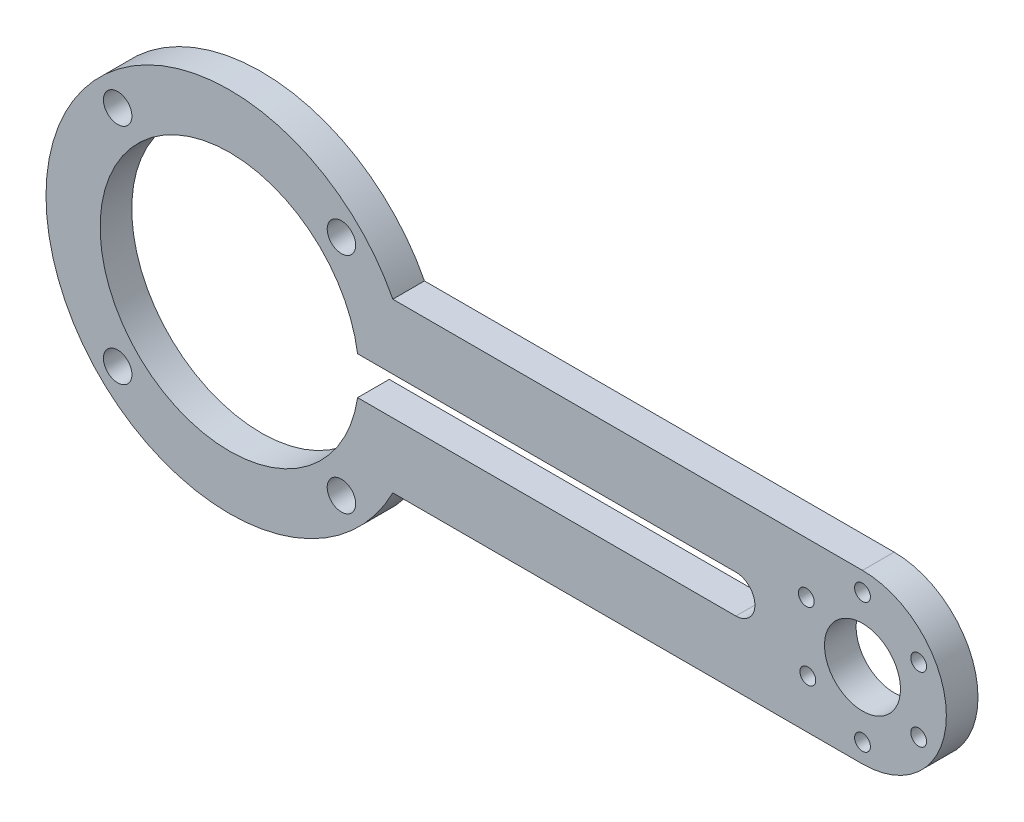
SolidWorks part; units mm, degrees
material "Wrought Stainless Steel"
ref_plane "Front Plane" through (0, 0, 0) normal (0, 0, 1) x (1, 0, 0)
ref_plane "Top Plane" through (0, 0, 0) normal (0, 1, 0) x (1, 0, 0)
ref_plane "Right Plane" through (0, 0, 0) normal (1, 0, 0) x (0, 0, -1)
sketch "Sketch2" plane through (0, 0, 0) normal (0, 0, 1) x (1, 0, 0)
  line L0 (0, 13.25) -> (100, 13.25)
  line L1 (0, -13.25) -> (100, -13.25)
  line L2 (50, 0) -> (50, -3)
  line L3 (50, 0) -> (50, 3)
  line L4 (20, 3) -> (80, 3)
  line L5 (20, -3) -> (80, -3)
  circle A0 centre (0, 0) radius 29
  circle A1 centre (0, 0) radius 20.45
  circle A2 centre (0, 0) radius 13.25
  circle A3 centre (100, 0) radius 13.25
  circle A4 centre (80, 0) radius 3
  circle A5 centre (20, 0) radius 3
  circle A6 centre (100, 0) radius 6
  point P18 (50, 3)
  point P20 (50, -3)
extrude "Boss-Extrude1" add sketch "Sketch2" along normal blind 5 contours A1 L0 A0 L1 | A1 L1 A0 L5 | A1 L4 A0 L0 | A4 L5 A0 L1 A3 L0 L4 | A3 A6 region at (-21.2479, 0, 0) region at (23.0197, 8.268, 0) region at (62.898, 12.4621, 0) region at (23.0197, -8.268, 0) region at (109.1042, 9.1042, 0)
sketch "Sketch3" plane through (0, 0, 5) normal (0, 0, 1) x (1, 0, 0)
  line L0 (0, 0) -> (17.6777, 17.6777)
  line L1 (0, 0) -> (17.6777, -17.6777)
  line L2 (0, 0) -> (-17.6777, -17.6777)
  line L3 (0, 0) -> (-17.6777, 17.6777)
  line L4 (100, 0) -> (108.8768, 5.125)
  line L5 (100, 0) -> (108.8768, -5.125)
  line L6 (100, 0) -> (100, -10.25)
  line L7 (100, 0) -> (91.1232, -5.125)
  line L8 (100, 0) -> (91.1232, 5.125)
  circle A0 centre (0, 0) radius 25
  circle A1 centre (17.6777, 17.6777) radius 2.25
  circle A2 centre (17.6777, -17.6777) radius 2.25
  circle A3 centre (-17.6777, -17.6777) radius 2.25
  circle A4 centre (-17.6777, 17.6777) radius 2.25
  circle A5 centre (100, 0) radius 10.25
  circle A6 centre (100, 10.25) radius 1.25
  circle A7 centre (108.8768, 5.125) radius 1.25
  circle A8 centre (91.1232, 5.125) radius 1.25
  circle A9 centre (91.3623, -5.5184) radius 1.25
  circle A10 centre (108.8768, -5.125) radius 1.25
  circle A11 centre (100, -10.25) radius 1.25
extrude "Cut-Extrude1" cut sketch "Sketch3" against normal through all contours A8 | A6 | A7 | A10 | A11 | A9 | A1 | A2 | A3 | A4
